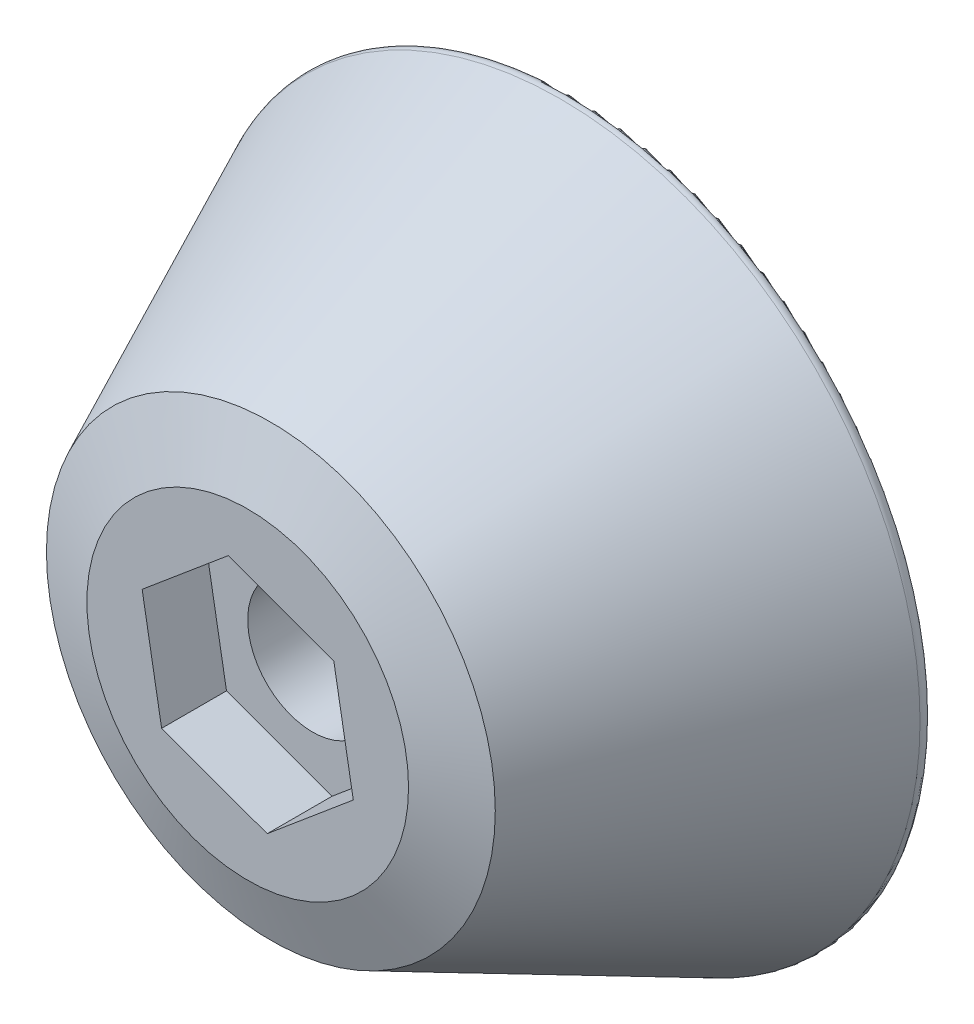
SolidWorks part; units mm, degrees
ref_plane "Front Plane" through (0, 0, 0) normal (0, 0, 1) x (1, 0, 0)
ref_plane "Top Plane" through (0, 0, 0) normal (0, 1, 0) x (1, 0, 0)
ref_plane "Right Plane" through (0, 0, 0) normal (1, 0, 0) x (0, 0, -1)
sketch "Sketch1" plane through (0, 0, 0) normal (0, 0, 1) x (1, 0, 0)
  circle A0 centre (0, 0) radius 28.575
  dimension "D1" = 57.15
extrude "Cone Extrude" add sketch "Sketch1" along normal blind 25.4 draft 25
chamfer "Chamfer1" distance 2 angle 45 1 edges at (16.7308, 0, 25.4) first distance on face at (16.7308, 0, 25.4)
sketch "Sketch3" plane through (0, 0, 25.4) normal (0, 0, 1) x (1, 0, 0)
  line L1 (6.7416, 5.6542) -> (-1.5259, 8.6655)
  line L2 (-1.5259, 8.6655) -> (-8.2675, 3.0113)
  line L3 (-8.2675, 3.0113) -> (-6.7416, -5.6542)
  line L4 (-6.7416, -5.6542) -> (1.5259, -8.6655)
  line L5 (1.5259, -8.6655) -> (8.2675, -3.0113)
  line L6 (8.2675, -3.0113) -> (6.7416, 5.6542)
  circle A0 centre (0, 0) radius 7.62 construction
  dimension "D1" = 15.24
extrude "Nut Hole Cut" cut sketch "Sketch3" against normal blind 5.08
sketch "Sketch4" plane through (0, 0, 20.32) normal (0, 0, 1) x (1, 0, 0)
  circle A0 centre (0, 0) radius 5.08
extrude "Cut-Extrude2" cut sketch "Sketch4" against normal through all
fillet "Fillet2" radius 0.635 1 edges at (28.575, 0, 0)
